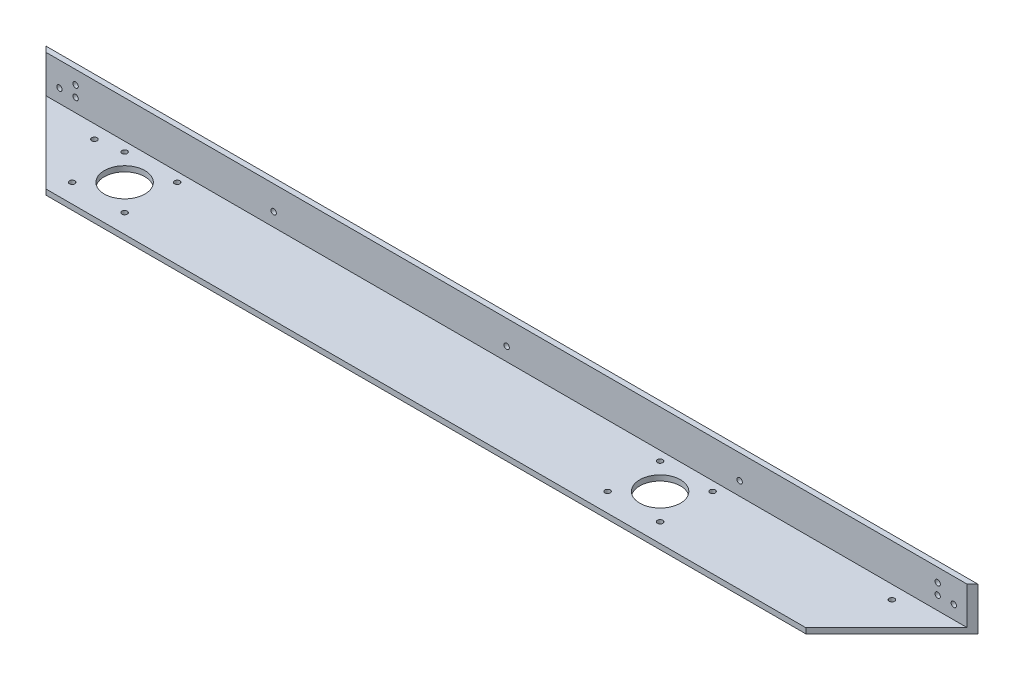
SolidWorks part; units mm, degrees
ref_plane "Front Plane" through (0, 0, 0) normal (0, 0, 1) x (1, 0, 0)
ref_plane "Top Plane" through (0, 0, 0) normal (0, 1, 0) x (1, 0, 0)
ref_plane "Right Plane" through (0, 0, 0) normal (1, 0, 0) x (0, 0, -1)
sketch "Sketch1" plane through (0, 0, 0) normal (1, 0, 0) x (0, 0, -1)
  line L0 (0, 0) -> (-50.8, 0)
  line L1 (-50.8, 0) -> (-50.8, 3.175)
  line L2 (-50.8, 3.175) -> (-3.175, 3.175)
  line L3 (-3.175, 3.175) -> (-3.175, 25.4)
  line L4 (-3.175, 25.4) -> (0, 25.4)
  line L5 (0, 25.4) -> (0, 0)
  dimension "LHeight" = 25.4
  dimension "LWidth" = 50.8
  dimension "LMaterialThickness" = 3.175
  dimension "D1" = 47.625
  dimension "D2" = 22.225
  dimension "D3" = 3.175
extrude "Boss-Extrude1" add sketch "Sketch1" along normal blind 550
chamfer "Chamfer7" distance 50.8 angle 45 1 edges at (0, 1.5875, 50.8)
chamfer "Chamfer8" distance 50.8 angle 45 1 edges at (550, 1.5875, 50.8)
sketch "BotthomHoles-Sketch2" plane through (0, 3.175, 0) normal (0, 1, 0) x (1, 0, 0)
  line L0 (546.825, -3.175) -> (3.175, -3.175) construction
  line L1 (550, 0) -> (0, 0) construction
  circle A0 centre (70.575, -24.175) radius 12
  circle A1 centre (386.575, -24.175) radius 12
  circle A2 centre (55.075, -8.675) radius 1.5875
  circle A3 centre (86.075, -8.675) radius 1.5875
  circle A4 centre (371.075, -8.675) radius 1.5875
  circle A5 centre (402.075, -8.675) radius 1.5875
  circle A6 centre (55.075, -39.675) radius 1.5875
  circle A7 centre (86.075, -39.675) radius 1.5875
  circle A8 centre (371.075, -39.675) radius 1.5875
  circle A9 centre (402.075, -39.675) radius 1.5875
  circle A10 centre (39.6875, -11.1125) radius 1.5875
  circle A11 centre (510.3125, -11.1125) radius 1.5875
  dimension "D9" = 3.175
  dimension "D10" = 24
  dimension "D14" = 3.175
  dimension "D2" = 8.675
  dimension "D3" = 31
  dimension "D4" = 15.5
  dimension "D5" = 15.5
  dimension "D6" = 31
  dimension "D7" = 15.5
  dimension "D8" = 31
  dimension "D11" = 21
  dimension "D12" = 316
  dimension "D13" = 70.575
  dimension "D15" = 39.6875
  dimension "D16" = 11.1125
  dimension "D17" = 39.6875
extrude "BottomHoles-Cut-Extrude1" cut sketch "BotthomHoles-Sketch2" against normal through all
sketch "LeftSideHoles-Sketch3" plane through (0, 0, 0) normal (0, 0, -1) x (-1, 0, 0)
  line L0 (0, 0) -> (0, 25.4) construction
  line L1 (-550, 0) -> (-550, 25.4) construction
  line L2 (-550, 25.4) -> (0, 25.4) construction
  circle A1 centre (-529.3625, 17.4625) radius 1.5875
  circle A2 centre (-538.8875, 11.1125) radius 1.5875
  circle A3 centre (-529.3625, 11.1125) radius 1.5875
  circle A4 centre (-11.1125, 11.1125) radius 1.5875
  circle A5 centre (-20.6375, 11.1125) radius 1.5875
  circle A6 centre (-20.6375, 17.4625) radius 1.5875
  circle A8 centre (-412.5, 11.1125) radius 1.5875
  circle A9 centre (-275, 11.1125) radius 1.5875
  circle A10 centre (-137.5, 11.1125) radius 1.5875
  dimension "D7" = 3.175
  dimension "D2" = 20.6375
  dimension "D4" = 11.1125
  dimension "D6" = 20.6375
  dimension "D8" = 137.5
  dimension "D9" = 137.5
  dimension "D10" = 137.5
  dimension "D5" = 11.1125
  dimension "D11" = 11.1125
  dimension "D3" = 7.9375
extrude "LeftSideHoles-Cut-Extrude2" cut sketch "LeftSideHoles-Sketch3" against normal through all
equation "\"LowerRailWidth\"= 2.00in"
equation "\"LowerRailHeight\"= 1.00in"
equation "\"RailThickness\"= .125in'Spec"
equation "\"SideRailHoleY1FromEdge\"= \"HoleOffsetFromEdge\""
equation "\"SideRailHoleX1FromSide\"= \"HoleOffsetFromSide\""
equation "\"StepperHoleDiameter\"= 24mm"
equation "\"StepperMountingHoleDiameter\"= 3.175mm"
equation "\"SideRailLength\"= 550mm"
equation "\"StepperMountingHoleDistance\"= 31mm'Spec"
equation "\"VSWidth\"= 1.25in'Spec"
equation "\"StepperMountingHoleOffsetFromLeftOrRightSide\"= \"StepperMountingHoleOffsetFromItsSide\" + \"RailThickness\""
equation "\"HoleOffsetFromEdge\"= \"RailThickness\" * 2.5"
equation "\"HoleOffsetFromSide\"= \"RailThickness\" * 3.5"
equation "\"StepperMountingHoleOffsetFromItsSide\"= 5.5mm'Spec"
equation "\"SideRailHoleX2FromSide\"= \"VSWidth\" - \"HoleOffsetFromEdge\" - \"RailThickness\"'Equals 20.6375"
equation "\"FasteningHoleDiameter\"= .125in"
equation "\"SideRailHoleY2FromSide\"= \"HoleOffsetFromSide\""
equation "\"LHeight@Sketch1\"=\"LowerRailHeight\""
equation "\"LWidth@Sketch1\"=\"LowerRailWidth\""
equation "\"D1@Chamfer7\"=\"LowerRailWidth\""
equation "\"D1@Chamfer8\"=\"LowerRailWidth\""
equation "\"D2@BotthomHoles-Sketch2\" = \"StepperMountingHoleOffsetFromLeftOrRightSide\""
equation "\"D3@BotthomHoles-Sketch2\" = \"StepperMountingHoleDistance\""
equation "\"D4@BotthomHoles-Sketch2\" = \"StepperMountingHoleDistance\" / 2"
equation "\"D5@BotthomHoles-Sketch2\"= \"StepperMountingHoleDistance\" / 2"
equation "\"D6@BotthomHoles-Sketch2\" = \"StepperMountingHoleDistance\""
equation "\"D7@BotthomHoles-Sketch2\" = \"StepperMountingHoleDistance\" / 2"
equation "\"D8@BotthomHoles-Sketch2\" = \"StepperMountingHoleDistance\""
equation "\"D9@BotthomHoles-Sketch2\" = \"StepperMountingHoleDiameter\""
equation "\"D10@BotthomHoles-Sketch2\" = \"StepperHoleDiameter\""
equation "\"D2@LeftSideHoles-Sketch3\" = \"SideRailHoleX2FromSide\""
equation "\"D4@LeftSideHoles-Sketch3\" = \"SideRailHoleY2FromSide\""
equation "\"D7@LeftSideHoles-Sketch3\" = \"FasteningHoleDiameter\""
equation "\"D1@Boss-Extrude1\"=\"SideRailLength\""
equation "\"D6@LeftSideHoles-Sketch3\"=\"SideRailHoleX2FromSide\""
equation "\"DistanceBetweenFrontToBackStepperHoles\"= \"BedLength\" - \"DistanceFromBedFrontToFirstLeftStepperHole\"'Equals 316"
equation "\"BedOverlap\"= 20mm"
equation "\"BedThirdSize\"= 70mm"
equation "\"BedLWidth\"= \"BedThirdSize\" + \"BedOverlap\"'Equals 90"
equation "\"BedInnerSquareWidth\"= \"BedThirdSize\" * 3'Equals 210"
equation "\"BedInnerSquareLength\"= \"BedInnerSquareWidth\""
equation "\"BedLength\"= \"BedInnerSquareLength\" + \"BedLWidth\" * 2 - \"BedOverlap\" * 2 + \"BedIncreasedByLength\"'Equals 350"
equation "\"D12@BotthomHoles-Sketch2\"=\"DistanceBetweenFrontToBackStepperHoles\""
equation "\"DistanceFromFrontSideToFirstLeftStepperHole\"= \"DistanceFromFrontSideToBedFront\" + \"DistanceFromBedFrontToFirstLeftStepperHole\"'Equals 70.575"
equation "\"D13@BotthomHoles-Sketch2\"=\"DistanceFromFrontSideToFirstLeftStepperHole\""
equation "\"DistanceFromBedFrontToFirstLeftStepperHole\"= \"LeadScrewNutPadSize\" + 10mm'Equals 34"
equation "\"DistanceFromFrontSideToBedFront\"= \"RailThickness\" + \"BeltTensionerDepth\" + 10mm'Equals 36.575"
equation "\"BeltTensionerDepth\"= \"BeltTensionerBackWallThickness\" + \"BeltTensionerInnerDepth\"'Equals 23.4"
equation "\"BeltTensionerBackWallThickness\"= 4mm"
equation "\"20TGT2PulleyDiameter\"= 17.9mm'Spec"
equation "\"BeltTensionerSpaceBetweenPulleyAndWall\"= 1.5mm"
equation "\"BeltTensionerInnerDepth\"= \"20TGT2PulleyDiameter\" + \"BeltTensionerSpaceBetweenPulleyAndWall\""
equation "\"BedIncreasedByLength\"= 0mm"
equation "\"LowerCornerBlockWidth\"= \"LowerRailWidth\" - \"RailThickness\" * 2'Room for left front stepper"
equation "\"D14@BotthomHoles-Sketch2\"= \"FasteningHoleDiameter\""
equation "\"D15@BotthomHoles-Sketch2\"=\"LowerCornerBlockX1FromSide\""
equation "\"D16@BotthomHoles-Sketch2\"= \"LowerCornerBlockY1FromSide\""
equation "\"D17@BotthomHoles-Sketch2\"=\"LowerCornerBlockX1FromSide\""
equation "\"LowerCornerBlockY1FromSide\"= \"HoleOffsetFromSide\""
equation "\"LowerCornerBlockX1FromSide\"= \"LowerCornerBlockWidth\" - \"HoleOffsetFromEdge\" + \"RailThickness\""
equation "\"LeadScrewNutMountingHoleFlangeDiameter\"= 22mm'Spec"
equation "\"LeadScrewNutPadSize\"= \"LeadScrewNutMountingHoleFlangeDiameter\" + 2mm'Equals 24"
equation "\"LeftOrRightEnclosureOffsets\"= \"SideRailLength\" / 4"
equation "\"D8@LeftSideHoles-Sketch3\"=\"LeftOrRightEnclosureOffsets\""
equation "\"D9@LeftSideHoles-Sketch3\"=\"LeftOrRightEnclosureOffsets\""
equation "\"D10@LeftSideHoles-Sketch3\"=\"LeftOrRightEnclosureOffsets\""
equation "\"D5@LeftSideHoles-Sketch3\"=\"SideRailHoleX1FromSide\""
equation "\"D11@LeftSideHoles-Sketch3\"=\"SideRailHoleX1FromSide\""
equation "\"D3@LeftSideHoles-Sketch3\"=\"SideRailHoleY1FromEdge\""
